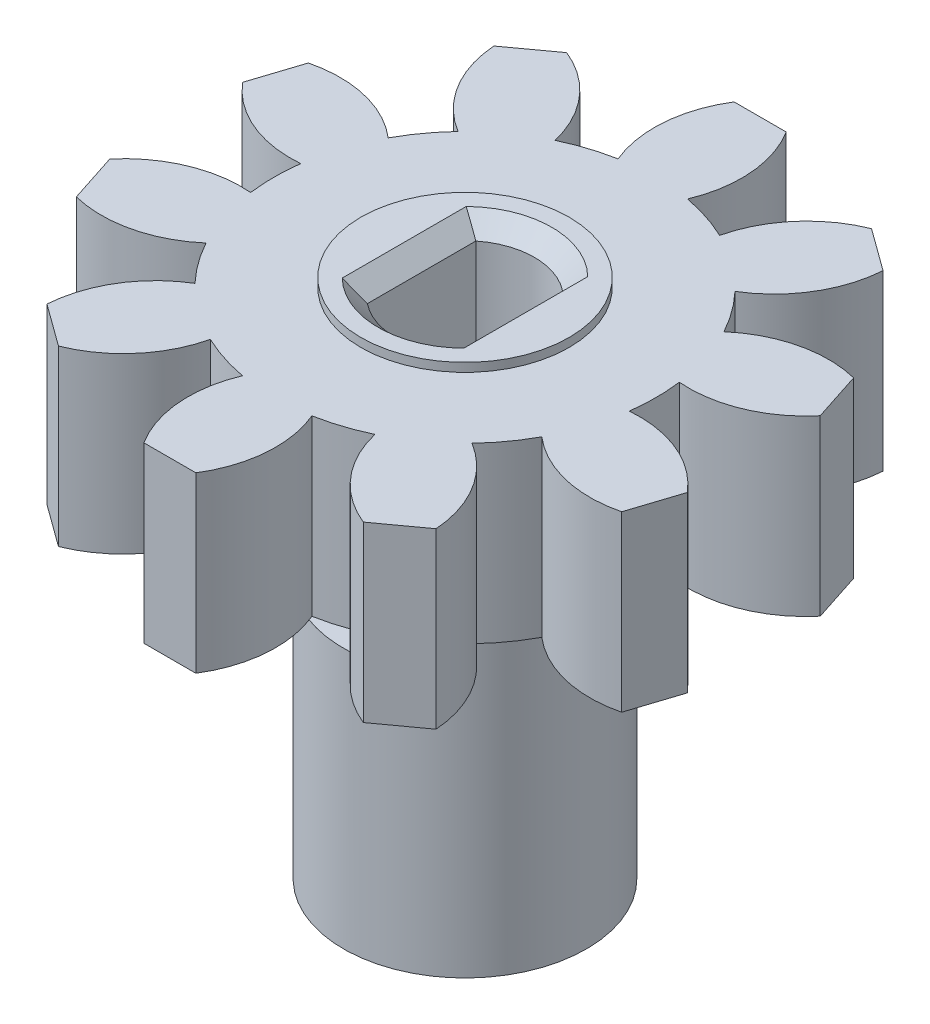
SolidWorks part; units mm, degrees
ref_plane "前视基准面" through (0, 0, 0) normal (0, 0, 1) x (1, 0, 0)
ref_plane "上视基准面" through (0, 0, 0) normal (0, 1, 0) x (1, 0, 0)
ref_plane "右视基准面" through (0, 0, 0) normal (1, 0, 0) x (0, 0, -1)
sketch "草图1" plane through (0, 0, 0) normal (0, 1, 0) x (1, 0, 0)
  circle A0 centre (0, 0) radius 5.5
extrude "凸台-拉伸1" add sketch "草图1" along normal blind 5
sketch "草图2" plane through (0, 5, 0) normal (0, 1, 0) x (-1, 0, 0)
  line L0 (-4.3894, -7.3175) -> (-5.6029, -6.4358)
  line L1 (-7.8522, -3.3399) -> (-8.3157, -1.9134)
  line L2 (-8.3157, 1.9134) -> (-7.8522, 3.3399)
  line L3 (-5.6029, 6.4358) -> (-4.3894, 7.3175)
  line L4 (-0.75, 8.5) -> (0.75, 8.5)
  line L5 (4.3894, 7.3175) -> (5.6029, 6.4358)
  line L6 (0.75, -8.5) -> (-0.75, -8.5)
  line L7 (7.8522, 3.3399) -> (8.3157, 1.9134)
  line L8 (8.3157, -1.9134) -> (7.8522, -3.3399)
  line L9 (5.6029, -6.4358) -> (4.3894, -7.3175)
  arc A0 (-1, -5.4083) -> (1, -5.4083) centre (0, 0) ccw
  arc A1 (-1, -5.4083) -> (-0.75, -8.5) centre (2.1122, -6.7126) ccw
  arc A2 (1, -5.4083) -> (0.75, -8.5) centre (-2.1122, -6.7126) cw
  arc A3 (-3.988, -3.7876) -> (-2.3699, -4.9632) centre (0, 0) ccw
  arc A4 (-3.988, -3.7876) -> (-5.6029, -6.4358) centre (-2.2368, -6.6721) ccw
  arc A5 (-2.3699, -4.9632) -> (-4.3894, -7.3175) centre (-5.6543, -4.1891) cw
  arc A6 (-5.4526, -0.7202) -> (-4.8346, -2.6223) centre (0, 0) ccw
  arc A7 (-5.4526, -0.7202) -> (-8.3157, -1.9134) centre (-5.7314, -4.0831) ccw
  arc A8 (-4.8346, -2.6223) -> (-7.8522, -3.3399) centre (-7.0368, -0.0655) cw
  arc A9 (-4.8346, 2.6223) -> (-5.4526, 0.7202) centre (0, 0) ccw
  arc A10 (-4.8346, 2.6223) -> (-7.8522, 3.3399) centre (-7.0368, 0.0655) ccw
  arc A11 (-5.4526, 0.7202) -> (-8.3157, 1.9134) centre (-5.7314, 4.0831) cw
  arc A12 (-2.3699, 4.9632) -> (-3.988, 3.7876) centre (0, 0) ccw
  arc A13 (-2.3699, 4.9632) -> (-4.3894, 7.3175) centre (-5.6543, 4.1891) ccw
  arc A14 (-3.988, 3.7876) -> (-5.6029, 6.4358) centre (-2.2368, 6.6721) cw
  arc A15 (1, 5.4083) -> (-1, 5.4083) centre (0, 0) ccw
  arc A16 (1, 5.4083) -> (0.75, 8.5) centre (-2.1122, 6.7126) ccw
  arc A17 (-1, 5.4083) -> (-0.75, 8.5) centre (2.1122, 6.7126) cw
  arc A18 (3.988, 3.7876) -> (2.3699, 4.9632) centre (0, 0) ccw
  arc A19 (3.988, 3.7876) -> (5.6029, 6.4358) centre (2.2368, 6.6721) ccw
  arc A20 (2.3699, 4.9632) -> (4.3894, 7.3175) centre (5.6543, 4.1891) cw
  arc A21 (5.4526, 0.7202) -> (4.8346, 2.6223) centre (0, 0) ccw
  arc A22 (5.4526, 0.7202) -> (8.3157, 1.9134) centre (5.7314, 4.0831) ccw
  arc A23 (4.8346, 2.6223) -> (7.8522, 3.3399) centre (7.0368, 0.0655) cw
  arc A24 (4.8346, -2.6223) -> (5.4526, -0.7202) centre (0, 0) ccw
  arc A25 (4.8346, -2.6223) -> (7.8522, -3.3399) centre (7.0368, -0.0655) ccw
  arc A26 (5.4526, -0.7202) -> (8.3157, -1.9134) centre (5.7314, -4.0831) cw
  arc A27 (2.3699, -4.9632) -> (3.988, -3.7876) centre (0, 0) ccw
  arc A28 (2.3699, -4.9632) -> (4.3894, -7.3175) centre (5.6543, -4.1891) ccw
  arc A29 (3.988, -3.7876) -> (5.6029, -6.4358) centre (2.2368, -6.6721) cw
  point P5 (0, -8.5)
  point P13 (-4.9962, -6.8766)
  point P22 (-8.084, -2.6266)
  point P30 (-8.084, 2.6266)
  point P38 (-4.9962, 6.8766)
  point P46 (0, 8.5)
  point P54 (4.9962, 6.8766)
  point P62 (8.084, 2.6266)
  point P70 (8.084, -2.6266)
  point P78 (4.9962, -6.8766)
  dimension "D1" = 10
extrude "凸台-拉伸2" add sketch "草图2" against normal up to surface (5 mm away) up to face at (0, 0, 5.5)
sketch "草图3" plane through (0, 0, 0) normal (0, -1, 0) x (1, 0, 0)
  circle A0 centre (0, 0) radius 3.5
extrude "凸台-拉伸3" add sketch "草图3" along normal blind 10
sketch "草图4" plane through (0, 5, 0) normal (0, 1, 0) x (-1, 0, 0)
  line L2 (1.25, 1.5612) -> (1.25, -1.5612)
  line L4 (-1.25, 1.5612) -> (-1.25, -1.5612)
  arc A0 (-1.25, -1.5612) -> (1.25, -1.5612) centre (0, 0) ccw
  arc A1 (1.25, 1.5612) -> (-1.25, 1.5612) centre (0, 0) ccw
extrude "切除-拉伸1" cut sketch "草图4" against normal blind 5
sketch "草图5" plane through (0, 0, 0) normal (0, 0, 1) x (1, 0, 0)
  line L0 (-2.3699, 0) -> (-1, 0) construction
  line L1 (-1.25, 0) -> (1.25, 0)
  line L2 (-1.25, 0) -> (-1.25, -2.25)
  line L3 (-1.25, -2.25) -> (1.25, -2.25)
  line L4 (1.25, 0) -> (1.25, -2.25)
  line L5 (-3.5, 0) -> (3.5, 0) construction
  dimension "D1" = 2.25
extrude "切除-拉伸2" cut sketch "草图5" against normal up to next and the other way up to next
sketch "草图6" plane through (0, -10, 0) normal (0, -1, 0) x (1, 0, 0)
  line L0 (0, 0) -> (-1.5, 0) construction
  line L1 (-1.5, 0) -> (-1.5, 2)
  line L2 (-1.5, 0) -> (-1.5, -2)
  arc A0 (-1.5, -2) -> (-1.5, 2) centre (0, 0) ccw
  dimension "D1" = 5
  dimension "D2" = 1.5
extrude "切除-拉伸3" cut sketch "草图6" against normal blind 7.75
sketch "草图7" plane through (0, -10, 0) normal (0, -1, 0) x (1, 0, 0)
  circle A0 centre (0, 0) radius 3.5
  dimension "D1" = 7
extrude "切除-拉伸4" cut sketch "草图7" against normal blind 0.25
sketch "草图8" plane through (0, -9.75, 0) normal (0, -1, 0) x (1, 0, 0)
  circle A0 centre (0, 0) radius 2.5
extrude "切除-拉伸5" cut sketch "草图8" against normal blind 0.5
chamfer "倒角2" distance 0.5 angle 45 2 edges at (-1.5, -9.25, 0) (0, -9.75, -2.5)
sketch "草图9" plane through (0, 5, 0) normal (0, 1, 0) x (1, 0, 0)
  line L0 (-1.25, 1.5612) -> (-1.25, -1.5612)
  line L1 (-1.25, 1.5612) -> (-1.25, -1.5612) construction
  line L2 (1.25, 1.5612) -> (1.25, -1.5612)
  arc A0 (-1.25, -1.5612) -> (1.25, -1.5612) centre (0, 0) ccw
  circle A1 centre (0, 0) radius 3
  arc A2 (1.25, 1.5612) -> (-1.25, 1.5612) centre (0, 0) ccw
  dimension "D1" = 6
extrude "凸台-拉伸4" add sketch "草图9" along normal blind 0.25
chamfer "倒角3" distance 0.5 angle 45 4 edges at (1.25, 5.25, 0) (0, 5.25, 2) (-1.25, 5.25, 0) (0, 5.25, -2)
